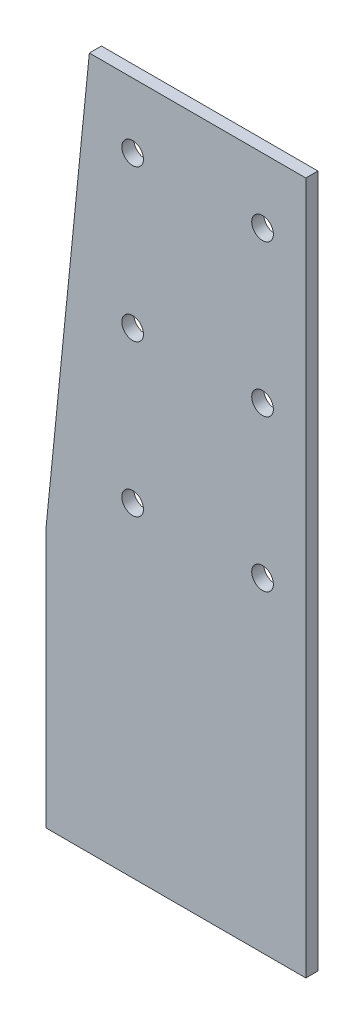
SolidWorks part; units mm, degrees
ref_plane "Front Plane" through (0, 0, 0) normal (0, 0, 1) x (1, 0, 0)
ref_plane "Top Plane" through (0, 0, 0) normal (0, 1, 0) x (1, 0, 0)
ref_plane "Right Plane" through (0, 0, 0) normal (1, 0, 0) x (0, 0, -1)
sketch "Sketch1" plane through (0, 0, 0) normal (0, 0, 1) x (1, 0, 0)
  line L1 (-42.9529, 356.7886) -> (-42.9529, 280.5886)
  line L2 (-42.9529, 280.5886) -> (33.2471, 280.5886)
  line L4 (33.2471, 483.7886) -> (-30.2529, 483.7886)
  line L5 (33.2471, 280.5886) -> (33.2471, 483.7886)
  line L6 (-42.9529, 356.7886) -> (-30.2529, 483.7886)
  circle A0 centre (-7.3929, 312.3386) radius 17.4625
  circle A1 centre (-17.5529, 375.8386) radius 3.175
  circle A2 centre (-17.5529, 420.2886) radius 3.175
  circle A3 centre (-17.5529, 464.7386) radius 3.175
  circle A4 centre (20.5471, 464.7386) radius 3.175
  circle A5 centre (20.5471, 420.2886) radius 3.175
  circle A6 centre (20.5471, 375.8386) radius 3.175
extrude "Boss-Extrude1" add sketch "Sketch1" along normal blind 3.556 contours L6 L4 L5 L2 L1
hole_wizard "1/4 (0.25) Diameter Hole1" positions "Sketch2" profile "Sketch3" hole size "1/4" standard "ANSI Inch"
sketch "Sketch2" plane through (-249.5393, -228.5115, -41.656) normal (0, 0, -1) x (-1, 0, 0)
  point P0 (-270.0863, 693.2501)
  point P3 (-231.9863, 693.2501)
  point P6 (-270.0863, 648.8001)
  point P9 (-231.9863, 648.8001)
  point P12 (-270.0863, 604.3501)
  point P15 (-231.9863, 604.3501)
sketch "Sketch3" plane through (20.5471, 464.7386, -41.656) normal (1, 0, 0) x (0, 1, 0)
  line L0 (0, 0) -> (0, 103.5077)
  line L1 (0, 103.5077) -> (3.175, 101.6)
  line L2 (3.175, 101.6) -> (3.175, 0)
  line L3 (3.175, 0) -> (0, 0)
  line L4 (0, 103.5077) -> (-3.175, 101.6) construction
  line L5 (0, -6.35) -> (0, 107.95) construction
  dimension "Hole Dia." = 6.35
  dimension "Hole Depth" = 101.6
  dimension "Drill Angle" = 118
hole_wizard "1/4 (0.25) Diameter Hole2" positions "Sketch4" profile "Sketch5" hole size "1/4" standard "ANSI Inch"
sketch "Sketch4" plane through (-249.5393, -228.5115, 0) normal (0, 0, -1) x (-1, 0, 0)
  point P0 (-270.0863, 693.2501)
  point P3 (-231.9863, 693.2501)
  point P6 (-270.0863, 648.8001)
  point P9 (-231.9863, 648.8001)
  point P12 (-270.0863, 604.3501)
  point P15 (-231.9863, 604.3501)
sketch "Sketch5" plane through (20.5471, 464.7386, 0) normal (1, 0, 0) x (0, 1, 0)
  line L0 (0, 0) -> (0, 103.5077)
  line L1 (0, 103.5077) -> (3.175, 101.6)
  line L2 (3.175, 101.6) -> (3.175, 0)
  line L3 (3.175, 0) -> (0, 0)
  line L4 (0, 103.5077) -> (-3.175, 101.6) construction
  line L5 (0, -6.35) -> (0, 107.95) construction
  dimension "Hole Dia." = 6.35
  dimension "Hole Depth" = 101.6
  dimension "Drill Angle" = 118
